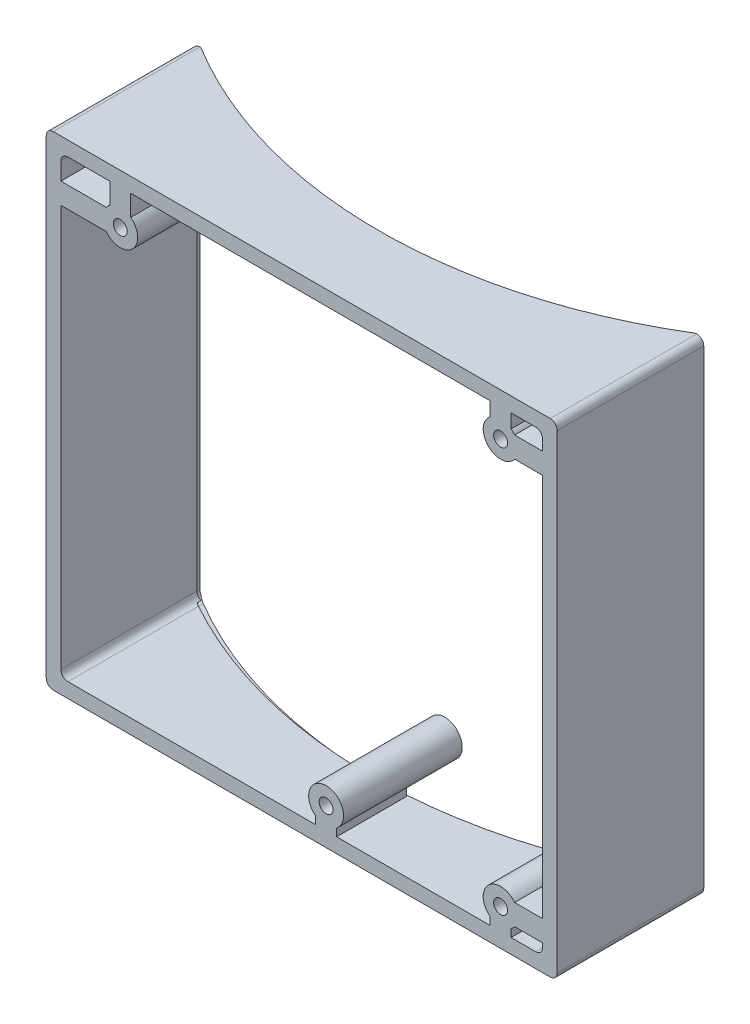
SolidWorks part; units mm, degrees
ref_plane "Ebene vorne" through (0, 0, 0) normal (0, 0, 1) x (1, 0, 0)
ref_plane "Ebene oben" through (0, 0, 0) normal (0, 1, 0) x (1, 0, 0)
ref_plane "Ebene rechts" through (0, 0, 0) normal (1, 0, 0) x (0, 0, -1)
sketch "Skizze1" plane through (0, 0, 0) normal (0, 0, 1) x (1, 0, 0)
  line L0 (-2.1, 67.2) -> (71.1, 67.2)
  line L1 (0, 0) -> (69, 0)
  line L2 (0, 0) -> (0, 65.1)
  line L3 (0, 65.1) -> (69, 65.1)
  line L4 (69, 0) -> (69, 65.1)
  line L5 (71.1, -2.1) -> (71.1, 67.2)
  line L6 (-2.1, -2.1) -> (71.1, -2.1)
  line L7 (-2.1, -2.1) -> (-2.1, 67.2)
  line L8 (-1.1, 66.2) -> (70.1, 66.2)
  line L9 (70.1, -1.1) -> (70.1, 66.2)
  line L10 (-1.1, -1.1) -> (70.1, -1.1)
  line L11 (-1.1, -1.1) -> (-1.1, 66.2)
  line L12 (8.5, 62.6) -> (8.5, 65.1)
  line L13 (65.5, 3.1) -> (69, 3.1)
  line L14 (65.5, 61.1) -> (69, 61.1)
  line L15 (38, 3.1) -> (63, 3.1) construction
  line L16 (7, 65.1) -> (7, 62.1)
  line L17 (65, 62.6) -> (69, 62.6)
  line L18 (65, 4.6) -> (69, 4.6)
  line L19 (38, 0.6) -> (38, 0)
  line L20 (36.5, 1.1) -> (36.5, 0)
  line L21 (6, 60.1) -> (0, 60.1)
  line L22 (0, 61.6) -> (6.5, 61.6)
  line L23 (63, 63.6) -> (63, 65.1)
  line L24 (61.5, 65.1) -> (61.5, 63.1)
  line L25 (0, 58.6) -> (6.5, 58.6)
  line L26 (10, 65.1) -> (10, 62.1)
  line L27 (64.5, 65.1) -> (64.5, 63.1)
  line L28 (65, 59.6) -> (69, 59.6)
  line L29 (39.5, 1.1) -> (39.5, 0)
  line L30 (65, 1.6) -> (69, 1.6)
  line L31 (63, 0.6) -> (63, 0)
  line L32 (64.5, 0) -> (64.5, 1.1)
  line L33 (61.5, 0) -> (61.5, 1.1)
  circle A0 centre (63, 61.1) radius 2.5
  circle A1 centre (63, 3.1) radius 2.5
  circle A2 centre (8.5, 60.1) radius 2.5
  circle A3 centre (38, 3.1) radius 2.5
  circle A4 centre (8.5, 60.1) radius 1
  circle A5 centre (63, 61.1) radius 1
  circle A6 centre (63, 3.1) radius 1
  circle A7 centre (38, 3.1) radius 1
  dimension "D8" = 5
  dimension "D9" = 5
  dimension "D10" = 54.5
  dimension "D11" = 25
  dimension "D12" = 5
  dimension "D13" = 5
  dimension "D24" = 5
  dimension "D2" = 69
  dimension "D5" = 58
  dimension "D6" = 4
  dimension "D7" = 6
  dimension "D14" = 66.2
  dimension "D15" = 71.2
  dimension "D18" = 5.1
  dimension "D19" = 1.5
  dimension "D20" = 1.5
  dimension "D21" = 1.5
  dimension "D22" = 1.5
  dimension "D23" = 1.5
  dimension "D25" = 1.5
  dimension "D3" = 2.1
  dimension "D4" = 1.1
extrude "Aufsatz-Linear austragen1" add sketch "Skizze1" against normal blind 17 contours A2 A4 | A0 A5 | A7 A3 | A1 A6 region at (36.9136, 5.2728, 0) region at (6.1954, 59.3318, 0) region at (61.2822, 4.8178, 0) region at (62.2318, 63.4046, 0)
extrude "Aufsatz-Linear austragen2" add sketch "Skizze1<3>" against normal blind 21 separate body contours L7 L6 L5 L0 L10 L11 L8 L9 region at (34.5, 67.0992, 0)
sketch "Skizze1<3>" plane through (0, 0, 0) normal (0, 0, 1) x (1, 0, 0) same geometry as "Skizze1"
extrude "Aufsatz-Linear austragen3" add sketch "Skizze1<4>" against normal blind 19.5 contours L11 L10 L9 L8 L4 L1 L2 L3 region at (34.5, 65.2203, 0)
sketch "Skizze1<4>" plane through (0, 0, 0) normal (0, 0, 1) x (1, 0, 0) same geometry as "Skizze1"
ref_plane "Ebene1" through (0, -2.1, 0) normal (0, -1, 0) x (-1, 0, 0)
sketch "Skizze2" plane through (0, -2.1, 0) normal (0, -1, 0) x (-1, 0, 0)
  line L0 (-34.5, 0) -> (-34.5, 46.3036) construction
  line L1 (2.1, 0) -> (-71.1, 0) construction
  line L2 (-34.5, 46.3036) -> (-34.5, 141.9857) construction
  line L3 (2.1, 21) -> (-71.1, 21) construction
  line L4 (2.1, 21) -> (-71.1, 21)
  line L5 (2.1, 20.538) -> (2.1, 21)
  line L6 (2.1, 21) -> (2.1, 0) construction
  line L7 (-71.1, 20.538) -> (-71.1, 21)
  line L8 (0.946, 21) -> (0.946, 19.8312)
  line L9 (-69.946, 21) -> (-69.946, 19.8312)
  circle A0 centre (-34.5, 79) radius 67.9737
  circle A1 centre (-34.5, 79) radius 68.9737
  point P15 (-69.946, 21)
  point P16 (0.946, 21)
  dimension "D1" = 1
  dimension "D2" = 58
extrude "Schnitt-Linear austragen1" cut sketch "Skizze2" against normal blind 2.1 contours L4 A0 region at (34.5, -2.1, -16.9843)
extrude "Schnitt-Linear austragen4" cut sketch "Skizze2<6>" against normal blind 1.2 from offset 1 contours L9 A1 L8 A0 region at (-0.2286, -2.1, -20.4156) offset against normal yes
sketch "Skizze2<6>" plane through (0, -2.1, 0) normal (0, -1, 0) x (-1, 0, 0) same geometry as "Skizze2"
extrude "Schnitt-Linear austragen6" cut sketch "Skizze2<14>" against normal blind 1.4 from offset 66.9 contours L9 A1 L8 A0 region at (-0.2286, -2.1, -20.4156) offset against normal yes
sketch "Skizze2<14>" plane through (0, -2.1, 0) normal (0, -1, 0) x (-1, 0, 0) same geometry as "Skizze2"
extrude "Aufsatz-Linear austragen4" add sketch "Skizze1<5>" against normal blind 10 contours A3 L20 L1 L19 | A3 L19 L1 L29 | A1 L33 L1 L31 | A1 L31 L1 L32 | A1 L13 L4 L18 | A1 L30 L4 L13 | A0 L14 L4 L17 | A0 L28 L4 L14 | A0 L27 L3 L23 | A0 L23 L3 L24 | A2 L12 L3 L16 | A2 L26 L3 L12 | A2 L22 L2 L21 | A2 L21 L2 L25 region at (37.1696, 0.3938, 0) region at (3.0814, 59.3401, 0) region at (38.8304, 0.3938, 0) region at (3.0814, 60.8599, 0) region at (62.1696, 0.3938, 0) region at (9.2729, 63.7663, 0) region at (63.8304, 0.3938, 0) region at (7.7271, 63.7663, 0) region at (67.1674, 3.8667, 0) region at (62.2132, 64.2638, 0) region at (67.1674, 2.3333, 0) region at (63.7868, 64.2638, 0) region at (67.1674, 60.3333, 0) region at (67.1674, 61.8667, 0)
sketch "Skizze1<5>" plane through (0, 0, 0) normal (0, 0, 1) x (1, 0, 0) same geometry as "Skizze1"
extrude "Schnitt-Linear austragen7" cut sketch "Skizze2<15>" against normal blind 10 from offset 66.9 contours L4 A0 region at (34.5, -2.1, -16.9843) offset against normal yes
sketch "Skizze2<15>" plane through (0, -2.1, 0) normal (0, -1, 0) x (-1, 0, 0) same geometry as "Skizze2"
fillet "Verrundung1" radius 1 8 edges at (0, 65.1, -9.6373) (69, 65.1, -9.6373) (69, 0, -9.6373) (0, 0, -9.6373) (-2.1, -2.1, -10.5) (71.1, -2.1, -10.5) (71.1, 67.2, -10.5) (-2.1, 67.2, -10.5)
fillet "Verrundung2" radius 1 4 edges at (70.1, 66.2, -20.25) (70.1, -1.1, -20.25) (-1.1, -1.1, -20.25) (-1.1, 66.2, -20.25)
